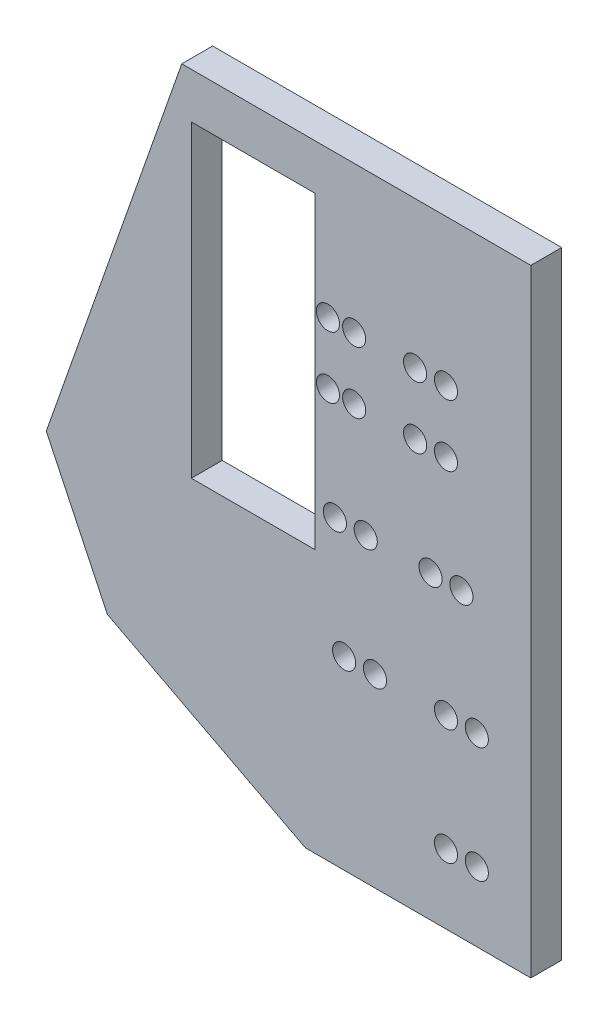
SolidWorks part; units mm, degrees
ref_plane "Front Plane" through (0, 0, 0) normal (0, 0, 1) x (1, 0, 0)
ref_plane "Top Plane" through (0, 0, 0) normal (0, 1, 0) x (1, 0, 0)
ref_plane "Right Plane" through (0, 0, 0) normal (1, 0, 0) x (0, 0, -1)
sketch "Sketch1" plane through (0, 0, 0) normal (0, 0, 1) x (1, 0, 0)
  line L6 (-20.066, -57.15) -> (46.99, -57.15) construction
  line L7 (-12.446, -73.152) -> (46.99, -73.152) construction
  line L8 (-4.1204, 6.35) -> (53.34, 6.35)
  line L9 (53.34, 6.35) -> (53.34, -95.25)
  line L10 (53.34, -95.25) -> (16.225, -95.25)
  line L16 (-4.1204, 6.35) -> (-26.416, -57.15)
  line L18 (-20.066, -57.15) -> (-26.416, -57.15) construction
  line L26 (0, 0) -> (46.99, 0) construction
  line L27 (46.99, 0) -> (46.99, -88.9) construction
  line L28 (46.99, -88.9) -> (17.78, -88.9) construction
  line L29 (17.78, -88.9) -> (-12.446, -73.152) construction
  line L30 (-12.446, -73.152) -> (-20.066, -57.15) construction
  line L31 (-20.066, -57.15) -> (0, 0) construction
  line L32 (46.99, -57.15) -> (46.99, -88.9) construction
  line L33 (17.78, -88.9) -> (16.225, -95.25) construction
  line L34 (-12.446, -73.152) -> (-17.9301, -78.4424) construction
  line L35 (16.225, -95.25) -> (-16.3566, -78.2747)
  line L36 (-26.416, -57.15) -> (-16.3566, -78.2747)
  point P40 (24.6098, 6.35)
  dimension "D1" = 88.9
  dimension "D2" = 29.21
  dimension "D3" = 59.436
  dimension "D4" = 67.056
  dimension "D5" = 6.35
  dimension "D6" = 6.35
  dimension "D7" = 46.99
  dimension "D8" = 6.35
  dimension "D13" = 103.76
  dimension "D14" = 6.35
  dimension "D17" = 108.51
  dimension "D22" = 5.7332
extrude "Boss-Extrude1" add sketch "Sketch1" along normal blind 5.08
sketch "Sketch3" plane through (0, 0, 0) normal (0, 0, 1) x (1, 0, 0)
  line L8 (0, 0) -> (46.99, 0) construction
  line L9 (46.99, 0) -> (46.99, -88.9) construction
  line L10 (46.99, -88.9) -> (17.78, -88.9) construction
  line L11 (17.78, -88.9) -> (-12.446, -73.152) construction
  line L12 (-12.446, -73.152) -> (-20.066, -57.15) construction
  line L13 (-20.066, -57.15) -> (0, 0) construction
sketch "Sketch4" plane through (0, 0, 0) normal (0, 0, -1) x (-1, 0, 0)
  line L8 (-17.78, -1.143) -> (2.54, -1.143)
  line L9 (-17.78, -1.143) -> (-17.78, -51.943)
  line L10 (-17.78, -51.943) -> (2.54, -51.943)
  line L11 (2.54, -1.143) -> (2.54, -51.943)
  circle A0 centre (-39.37, -17.78) radius 1.905
  circle A1 centre (-34.29, -17.78) radius 1.905
  circle A2 centre (-39.37, -27.94) radius 1.905
  circle A3 centre (-34.29, -27.94) radius 1.905
  circle A4 centre (-41.91, -45.72) radius 1.905
  circle A5 centre (-36.83, -45.72) radius 1.905
  circle A6 centre (-44.45, -64.77) radius 1.905
  circle A7 centre (-39.37, -64.77) radius 1.905
  circle A8 centre (-44.45, -83.82) radius 1.905
  circle A9 centre (-39.37, -83.82) radius 1.905
  circle A10 centre (-24.257, -17.78) radius 1.905
  circle A11 centre (-19.939, -17.78) radius 1.905
  circle A12 centre (-24.257, -27.94) radius 1.905
  circle A13 centre (-19.939, -27.94) radius 1.905
  circle A14 centre (-26.162, -45.72) radius 1.905
  circle A15 centre (-21.082, -45.72) radius 1.905
  circle A16 centre (-27.686, -64.77) radius 1.905
  circle A17 centre (-22.606, -64.77) radius 1.905
  dimension "D1" = 3.81
  dimension "D2" = 3.81
  dimension "D6" = 3.81
  dimension "D7" = 3.81
  dimension "D11" = 3.81
  dimension "D12" = 3.81
  dimension "D16" = 3.81
  dimension "D17" = 3.81
  dimension "D21" = 3.81
  dimension "D22" = 3.81
  dimension "D30" = 3.81
  dimension "D31" = 3.81
  dimension "D35" = 3.81
  dimension "D36" = 3.81
  dimension "D40" = 3.81
  dimension "D41" = 3.81
  dimension "D45" = 3.81
  dimension "D46" = 3.81
  dimension "D3" = 5.08
  dimension "D8" = 5.08
  dimension "D13" = 5.08
  dimension "D18" = 5.08
  dimension "D23" = 5.08
  dimension "D26" = 50.8
  dimension "D27" = 20.32
  dimension "D32" = 4.318
  dimension "D37" = 4.318
  dimension "D42" = 5.08
  dimension "D47" = 5.08
extrude "Cut-Extrude2" cut sketch "Sketch4" against normal blind 25.4
